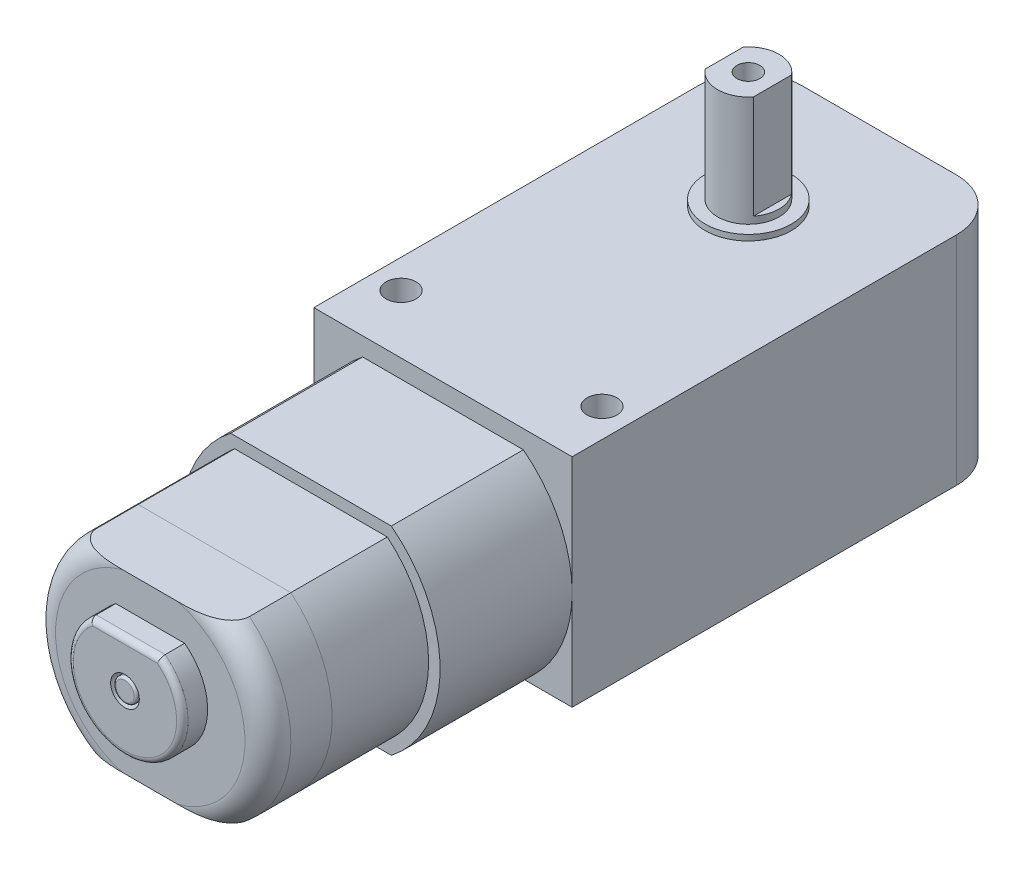
SolidWorks part; units mm, degrees
ref_plane "Front Plane" through (0, 0, 0) normal (0, 0, 1) x (1, 0, 0)
ref_plane "Top Plane" through (0, 0, 0) normal (0, 1, 0) x (1, 0, 0)
ref_plane "Right Plane" through (0, 0, 0) normal (1, 0, 0) x (0, 0, -1)
sketch "Sketch1" plane through (0, 0, 0) normal (0, 1, 0) x (1, 0, 0)
  line L1 (11.25, 19) -> (-11.25, 19)
  line L2 (11.25, 19) -> (11.25, -19)
  line L3 (11.25, -19) -> (-11.25, -19)
  line L4 (-11.25, 19) -> (-11.25, -19)
  line L5 (11.25, 19) -> (-11.25, -19) construction
  line L6 (11.25, -19) -> (-11.25, 19) construction
  point P0 (0, 0)
  dimension "D1" = 22.5
  dimension "D2" = 38
extrude "Boss-Extrude1" add sketch "Sketch1" along normal mid plane 18.9
fillet "Fillet1" radius 4.5 2 edges at (-11.25, 0, -19) (11.25, 0, -19)
sketch "Sketch2" plane through (0, 0, 19) normal (0, 0, 1) x (1, 0, 0)
  line L0 (-11.25, -9.45) -> (11.25, -9.45) construction
  line L5 (7, -9.45) -> (-7, -9.45)
  line L7 (7, 7.85) -> (-7, 7.85)
  line L9 (7, -9.45) -> (-7, 7.85) construction
  line L10 (7, 7.85) -> (-7, -9.45) construction
  line L13 (-11.25, 9.45) -> (-11.25, -9.45) construction
  arc A0 (-7, 7.85) -> (-7, -9.45) centre (-0.3224, -0.8) ccw
  arc A1 (7, 7.85) -> (7, -9.45) centre (0.3224, -0.8) cw
  point P0 (0, -0.8)
  dimension "D3" = 10.9276
  dimension "D1" = 17.3
  dimension "D2" = 14
extrude "Boss-Extrude2" add sketch "Sketch2" along normal blind 11.5
sketch "Sketch3" plane through (0, 0, 30.5) normal (0, 0, 1) x (1, 0, 0)
  line L4 (-6.6497, -8.45) -> (6.6497, -8.45)
  line L5 (6.6497, 6.85) -> (-6.6497, 6.85)
  line L6 (-6.6497, -8.45) -> (6.6497, -8.45)
  line L7 (6.6497, 6.85) -> (-6.6497, 6.85)
  arc A4 (-6.6497, 6.85) -> (-6.6497, -8.45) centre (-0.3224, -0.8) ccw
  arc A5 (6.6497, -8.45) -> (6.6497, 6.85) centre (0.3224, -0.8) ccw
  arc A6 (-6.6497, 6.85) -> (-6.6497, -8.45) centre (-0.3224, -0.8) ccw
  arc A7 (6.6497, -8.45) -> (6.6497, 6.85) centre (0.3224, -0.8) ccw
  dimension "D1" = 1
extrude "Cut-Extrude1" cut sketch "Sketch3" against normal up to surface (11.5 mm away) up to face at (0, 5.6646, 19)
sketch "Sketch4" plane through (0, 0, 0) normal (0, 1, 0) x (1, 0, 0)
  line L0 (6.75, 19) -> (-6.75, 19) construction
  line L1 (2.5, 19) -> (-2.5, 19)
  line L2 (2.5, 19) -> (2.5, 24)
  line L3 (2.5, 24) -> (-2.5, 24)
  line L4 (-2.5, 19) -> (-2.5, 24)
  line L5 (2.5, 19) -> (-2.5, 24) construction
  line L6 (2.5, 24) -> (-2.5, 19) construction
  circle A0 centre (0, 21.5) radius 1.25
  point P0 (0, 21.5)
  dimension "D3" = 2.5
  dimension "D1" = 5
  dimension "D2" = 5
extrude "Boss-Extrude3" add sketch "Sketch4" along normal mid plane 2.5 contours L4 L1 L2 L3 A0 | L4 L3 L2 L1 | A0 region at (0, 0, -19.0707)
sketch "Sketch5" plane through (0, 9.45, 0) normal (0, 1, 0) x (1, 0, 0)
  line L0 (0, 24) -> (0, 0) construction
  line L1 (2.5, 24) -> (-2.5, 24) construction
  line L2 (6.75, 19) -> (-6.75, 19) construction
  circle A0 centre (0, 7.6) radius 3.75
  dimension "D1" = 7.5
  dimension "D2" = 11.4
extrude "Boss-Extrude4" add sketch "Sketch5" along normal blind 0.5
sketch "Sketch6" plane through (0, 9.95, 0) normal (0, 1, 0) x (1, 0, 0)
  circle A0 centre (0, 7.6) radius 2.675
  dimension "D1" = 5.35
extrude "Boss-Extrude5" add sketch "Sketch6" along normal blind 9.6
sketch "Sketch7" plane through (0, 19.55, 0) normal (0, 1, 0) x (1, 0, 0)
  line L0 (-2.1, 9.257) -> (-2.1, 5.943)
  line L1 (2.1, 9.257) -> (2.1, 5.943)
  line L2 (-2.1, 7.6) -> (2.1, 7.6) construction
  circle A0 centre (0, 7.6) radius 2.675 construction
  circle A1 centre (0, 7.6) radius 2.675 construction
  arc A2 (2.1, 5.943) -> (2.1, 9.257) centre (0, 7.6) ccw
  circle A3 centre (0, 7.6) radius 2.675
  arc A4 (-2.1, 9.257) -> (-2.1, 5.943) centre (0, 7.6) ccw
  point P10 (0, 7.6)
  dimension "D2" = 4.2
  dimension "D1" = 0
extrude "Cut-Extrude4" cut sketch "Sketch7" against normal blind 9
sketch "Sketch8" plane through (0, 19.55, 0) normal (0, 1, 0) x (1, 0, 0)
  circle A0 centre (0, 7.6) radius 1
  dimension "D1" = 2
extrude "Cut-Extrude5" cut sketch "Sketch8" against normal up to surface (9 mm away) up to face at (-2.3875, 10.55, -7.6)
fillet "Fillet2" radius 0.5 2 edges at (2.5, 0, -24) (-2.5, 0, -24)
sketch "Sketch9" plane through (0, 0, 19) normal (0, 0, 1) x (1, 0, 0)
  line L2 (-6.6497, -8.45) -> (6.6497, -8.45)
  line L3 (6.6497, 6.85) -> (-6.6497, 6.85)
  line L4 (-6.6497, -8.45) -> (6.6497, -8.45)
  line L5 (6.6497, 6.85) -> (-6.6497, 6.85)
  arc A2 (-6.6497, 6.85) -> (-6.6497, -8.45) centre (-0.3224, -0.8) ccw
  arc A3 (6.6497, -8.45) -> (6.6497, 6.85) centre (0.3224, -0.8) ccw
  arc A4 (-6.6497, 6.85) -> (-6.6497, -8.45) centre (-0.3224, -0.8) ccw
  arc A5 (6.6497, -8.45) -> (6.6497, 6.85) centre (0.3224, -0.8) ccw
  dimension "D1" = 0
extrude "Boss-Extrude6" add sketch "Sketch9" along normal blind 27.7 separate body
sketch "Sketch10" plane through (0, 6.85, 0) normal (0, 1, 0) x (1, 0, 0)
  line L0 (-10.25, -38.9) -> (10.25, -38.9)
  line L1 (-10.25, -19) -> (-10.25, -46.7) construction
  line L2 (10.25, -46.7) -> (10.25, -19) construction
  line L3 (7, -30.5) -> (-7, -30.5) construction
  dimension "D1" = 8.4
split "Split1" trim tools "Sketch10" bodies to split 109 resulting bodies 110 111
sketch "Sketch11" plane through (0, 0, 46.7) normal (0, 0, 1) x (1, 0, 0)
  line L0 (-3, 4) -> (3, 4)
  line L3 (-6.6497, -8.45) -> (6.6497, -8.45)
  line L4 (6.6497, 6.85) -> (-6.6497, 6.85)
  line L5 (-6.6497, -8.45) -> (6.6497, -8.45)
  line L6 (6.6497, 6.85) -> (-6.6497, 6.85)
  arc A0 (-3, 4) -> (3, 4) centre (0, 0) ccw
  arc A3 (-6.6497, 6.85) -> (-6.6497, -8.45) centre (-0.3224, -0.8) ccw
  arc A7 (-6.6497, 6.85) -> (-6.6497, -8.45) centre (-0.3224, -0.8) ccw
  arc A9 (6.6497, -8.45) -> (6.6497, 6.85) centre (0.3224, -0.8) ccw
  arc A10 (6.6497, -8.45) -> (6.6497, 6.85) centre (0.3224, -0.8) ccw
  dimension "D1" = 10
  dimension "D2" = 9
  dimension "D3" = 0
extrude "Cut-Extrude6" cut sketch "Sketch11" against normal blind 2.2
fillet "Fillet4" radius 0.5 2 edges at (0, -5, 46.7) (0, 4, 46.7)
fillet "Fillet3" radius 2 2 edges at (-10.25, -0.8, 44.5) (10.25, -0.8, 44.5)
sketch "Sketch12" plane through (0, 0, 46.7) normal (0, 0, 1) x (1, 0, 0)
  circle A0 centre (0, 0) radius 1.25
  dimension "D1" = 2.5
extrude "Cut-Extrude7" cut sketch "Sketch12" against normal up to surface (2.2 mm away) up to face at (0, -0.5, 44.5)
sketch "Sketch13" plane through (0, 0, 44.5) normal (0, 0, 1) x (1, 0, 0)
  circle A0 centre (0, 0) radius 1
  dimension "D1" = 2
extrude "Boss-Extrude7" add sketch "Sketch13" along normal up to surface (2.2 mm away) up to face at (1.25, 0, 46.7)
fillet "Fillet5" radius 0.2 1 edges at (1, 0, 46.7)
sketch "Sketch14" plane through (0, 9.45, 0) normal (0, 1, 0) x (1, 0, 0)
  line L0 (-8.75, -13.9) -> (8.75, -13.9) construction
  line L1 (11.25, -19) -> (11.25, 14.5) construction
  line L4 (7, -19) -> (11.25, -19) construction
  circle A0 centre (-8.75, -13.9) radius 1.3
  circle A1 centre (8.75, -13.9) radius 1.3
  point P11 (0, -13.9)
  dimension "D1" = 2.6
  dimension "D2" = 2.5
  dimension "D3" = 5.1
extrude "Cut-Extrude8" cut sketch "Sketch14" against normal up to surface (18.9 mm away) up to face at (0, -9.45, 6.8136)
equation "\"D2@Sketch14\"= 1.2 + (\"D1@Sketch14\"/2)"
equation "\"D3@Sketch14\"=3.8 + (\"D1@Sketch14\"/2)"
